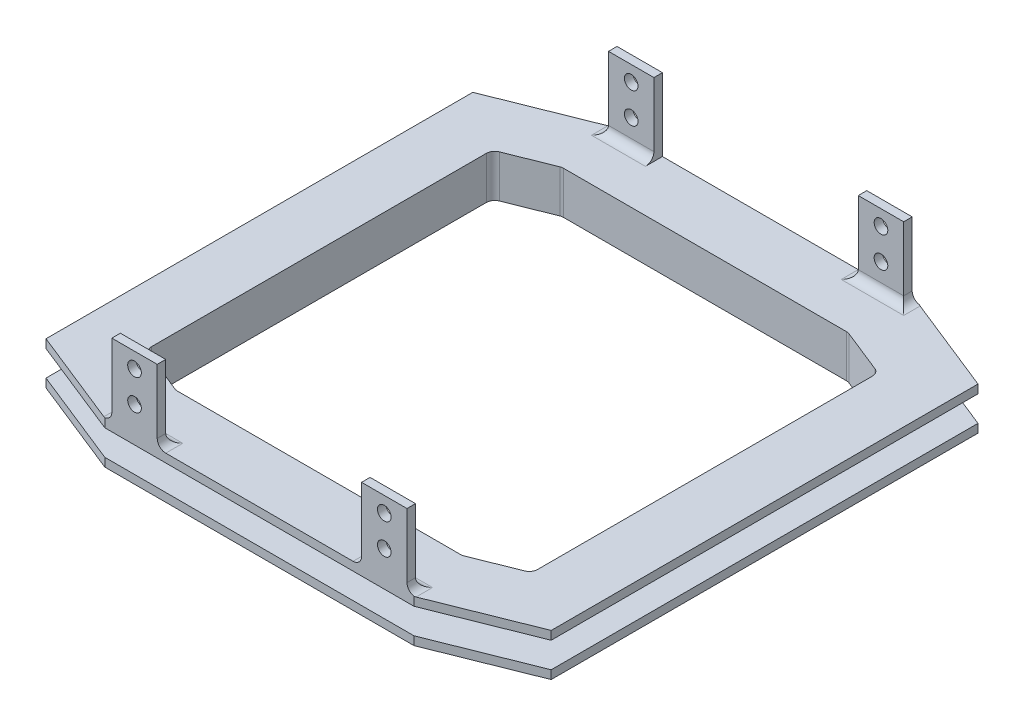
SolidWorks part; units mm, degrees
ref_plane "Front Plane" through (0, 0, 0) normal (0, 0, 1) x (1, 0, 0)
ref_plane "Top Plane" through (0, 0, 0) normal (0, 1, 0) x (1, 0, 0)
ref_plane "Right Plane" through (0, 0, 0) normal (1, 0, 0) x (0, 0, -1)
sketch "Sketch1" plane through (0, 0, 0) normal (0, 1, 0) x (1, 0, 0)
  line L5 (-35.5, 0) -> (0, 0) construction
  line L6 (-25.5, -35.5) -> (25.5, -35.5)
  line L10 (-35.5, -31.5) -> (-35.5, 31.5)
  line L11 (-25.5, 35.5) -> (25.5, 35.5)
  line L12 (35.5, -31.5) -> (35.5, 31.5)
  line L13 (0, 0) -> (0, 35.5) construction
  line L14 (25.5, -35.5) -> (35.5, -31.5)
  line L15 (25.5, 35.5) -> (35.5, 31.5)
  line L16 (-25.5, -35.5) -> (-35.5, -31.5)
  line L17 (-25.5, 35.5) -> (-35.5, 31.5)
  point P0 (0, 0)
  point P4 (35.5, -35.5)
  dimension "D3" = 4
  dimension "D2" = 10
  dimension "D4" = 71
extrude "Boss-Extrude1" add sketch "Sketch1" along normal mid plane 4.5
sketch "Sketch2" plane through (0, 2.25, 0) normal (0, 1, 0) x (1, 0, 0)
  line L16 (27.2332, -44.5) -> (44.5, -37.5933)
  line L17 (44.5, -37.5933) -> (44.5, 37.5933)
  line L18 (44.5, 37.5933) -> (27.2332, 44.5)
  line L19 (27.2332, 44.5) -> (-27.2332, 44.5)
  line L20 (-27.2332, 44.5) -> (-44.5, 37.5933)
  line L21 (-44.5, 37.5933) -> (-44.5, -37.5933)
  line L22 (-44.5, -37.5933) -> (-27.2332, -44.5)
  line L23 (-27.2332, -44.5) -> (27.2332, -44.5)
  line L24 (27.2332, -44.5) -> (44.5, -37.5933)
  line L25 (44.5, -37.5933) -> (44.5, 37.5933)
  line L26 (44.5, 37.5933) -> (27.2332, 44.5)
  line L27 (27.2332, 44.5) -> (-27.2332, 44.5)
  line L28 (-27.2332, 44.5) -> (-44.5, 37.5933)
  line L29 (-44.5, 37.5933) -> (-44.5, -37.5933)
  line L30 (-44.5, -37.5933) -> (-27.2332, -44.5)
  line L31 (-27.2332, -44.5) -> (27.2332, -44.5)
  dimension "D1" = 9
extrude "Boss-Extrude2" add sketch "Sketch2" along normal blind 1.5
mirror "Mirror1" about plane through (0, 0, 0) normal (0, 1, 0) of "Boss-Extrude2"
sketch "Sketch3" plane through (0, 0, 0) normal (0, 1, 0) x (1, 0, 0)
  line L16 (-25.2111, -34) -> (25.2111, -34)
  line L17 (25.2111, -34) -> (34, -30.4845)
  line L18 (34, -30.4845) -> (34, 30.4845)
  line L19 (34, 30.4845) -> (25.2111, 34)
  line L20 (25.2111, 34) -> (-25.2111, 34)
  line L21 (-25.2111, 34) -> (-34, 30.4845)
  line L22 (-34, 30.4845) -> (-34, -30.4845)
  line L23 (-34, -30.4845) -> (-25.2111, -34)
  line L24 (-25.2111, -34) -> (25.2111, -34)
  line L25 (25.2111, -34) -> (34, -30.4845)
  line L26 (34, -30.4845) -> (34, 30.4845)
  line L27 (34, 30.4845) -> (25.2111, 34)
  line L28 (25.2111, 34) -> (-25.2111, 34)
  line L29 (-25.2111, 34) -> (-34, 30.4845)
  line L30 (-34, 30.4845) -> (-34, -30.4845)
  line L31 (-34, -30.4845) -> (-25.2111, -34)
  dimension "D1" = 10.5
extrude "Cut-Extrude1" cut sketch "Sketch3" against normal through all both and the other way through all
sketch "Sketch5" plane through (0, 0, 0) normal (0, 0, 1) x (1, 0, 0)
  line L0 (0, 0) -> (0, 28.4264) construction
  line L1 (-27.2332, 3.75) -> (27.2332, 3.75) construction
  line L2 (-26, 3.75) -> (-18, 3.75)
  line L3 (-26, 3.75) -> (-26, 16.55)
  line L4 (-26, 16.55) -> (-18, 16.55)
  line L5 (-18, 3.75) -> (-18, 16.55)
  line L6 (-22, 16.55) -> (-22, 9.7096) construction
  line L7 (18, 3.75) -> (18, 16.55)
  line L8 (26, 16.55) -> (18, 16.55)
  line L9 (26, 3.75) -> (26, 16.55)
  line L10 (26, 3.75) -> (18, 3.75)
  dimension "D1" = 22
  dimension "D3" = 12.8
  dimension "D2" = 8
extrude "Boss-Extrude3" add sketch "Sketch5" against normal blind 1.5 from surface starting at face at (0, 3, 44.5)
extrude "Boss-Extrude4" add sketch "Sketch5<2>" along normal blind 1.5 from surface starting at face at (0, 3, -44.5)
sketch "Sketch5<2>" plane through (0, 0, 0) normal (0, 0, 1) x (1, 0, 0) same geometry as "Sketch5"
sketch "Sketch6" plane through (0, 0, 0) normal (0, 0, 1) x (1, 0, 0)
  line L0 (-22, 16.55) -> (-22, 13.85) construction
  line L1 (-18, 16.55) -> (-26, 16.55) construction
  line L2 (0, 0) -> (0, 25.5714) construction
  line L3 (-22, 13.85) -> (-22, 8.45) construction
  circle A0 centre (-22, 13.85) radius 1.2
  circle A1 centre (22, 13.85) radius 1.2
  circle A2 centre (-22, 8.45) radius 1.2
  circle A3 centre (22, 8.45) radius 1.2
  dimension "D1" = 2.4
  dimension "D2" = 2.7
  dimension "D3" = 5.4
extrude "Cut-Extrude3" cut sketch "Sketch6" against normal through all both and the other way through all
fillet "Fillet1" radius 1.5 35 edges at (35.5, 0, 31.5) (25.5, 0, 35.5) (0, 2.25, -35.5) (0, -2.25, -35.5) (35.5, 2.25, 0) (35.5, -2.25, 0) (-35.5, 2.25, 0) (-35.5, -2.25, 0) (0, 2.25, 35.5) (0, -2.25, 35.5) (-25.5, 0, -35.5) (-30.5, 2.25, -33.5) (-35.5, 0, -31.5) (-30.5, -2.25, -33.5) (35.5, 0, -31.5) (30.5, 2.25, -33.5) (25.5, 0, -35.5) (30.5, -2.25, -33.5) (30.5, 2.25, 33.5) (30.5, -2.25, 33.5) (-35.5, 0, 31.5) (-30.5, 2.25, 33.5) (-25.5, 0, 35.5) (-30.5, -2.25, 33.5) (-22, 3.75, -43) (22, 3.75, -43) (-22, 3.75, 43) (22, 3.75, 43) (26, 3.75, 43.75) (-18, 3.75, 43.75) (18, 3.75, 43.75) (-26, 3.75, 43.75) (18, 3.75, -43.75) (26, 3.75, -43.75) (-26, 3.75, -43.75)
fillet "Fillet2" radius 1.5 8 edges at (-25.2111, 0, -34) (-34, 0, -30.4845) (25.2111, 0, -34) (34, 0, -30.4845) (25.2111, 0, 34) (34, 0, 30.4845) (-25.2111, 0, 34) (-34, 0, 30.4845)
